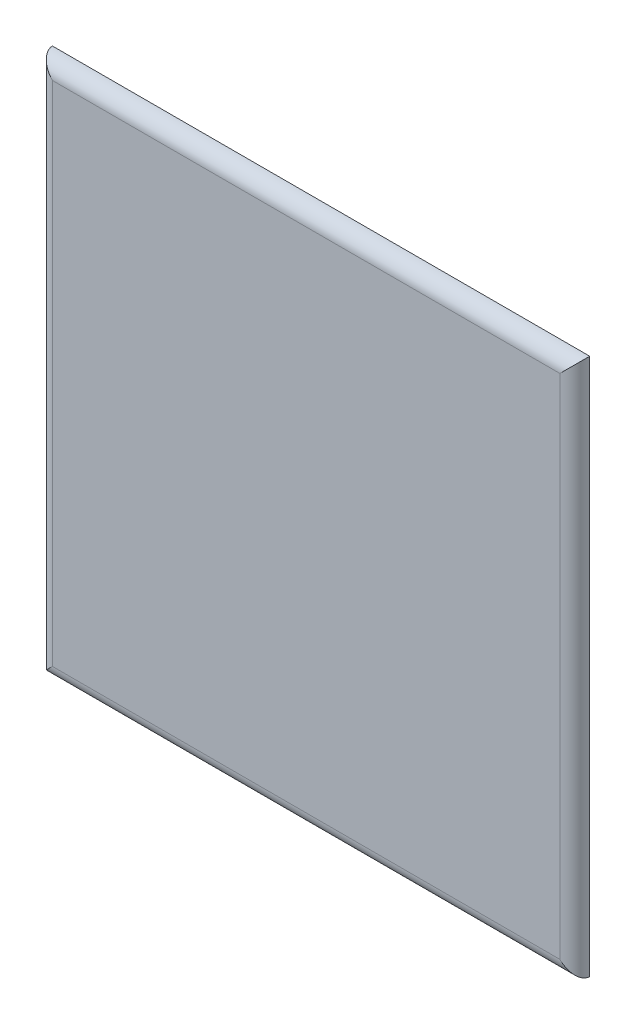
SolidWorks part; units mm, degrees
material "PS HI"
ref_plane "Ön Düzlem" through (0, 0, 0) normal (0, 0, 1) x (1, 0, 0)
ref_plane "Üst Düzlem" through (0, 0, 0) normal (0, 1, 0) x (1, 0, 0)
ref_plane "Sağ Düzlem" through (0, 0, 0) normal (1, 0, 0) x (0, 0, -1)
sketch "Çizim1" plane through (0, 0, 0) normal (0, 0, 1) x (1, 0, 0)
  line L1 (-9, -9) -> (9, -9)
  line L2 (-9, -9) -> (-9, 9)
  line L3 (-9, 9) -> (9, 9)
  line L4 (9, -9) -> (9, 9)
  line L5 (-9, -9) -> (9, 9) construction
  line L6 (-9, 9) -> (9, -9) construction
  point P0 (0, 0)
  dimension "D1" = 18
  dimension "D2" = 18
extrude "Yükseklik-Ekstrüzyon1" add sketch "Çizim1" along normal mid plane 0.5
fillet "Radyus1" radius 0.5 4 edges at (9, 0, 0.25) (0, -9, 0.25) (-9, 0, 0.25) (0, 9, 0.25)
